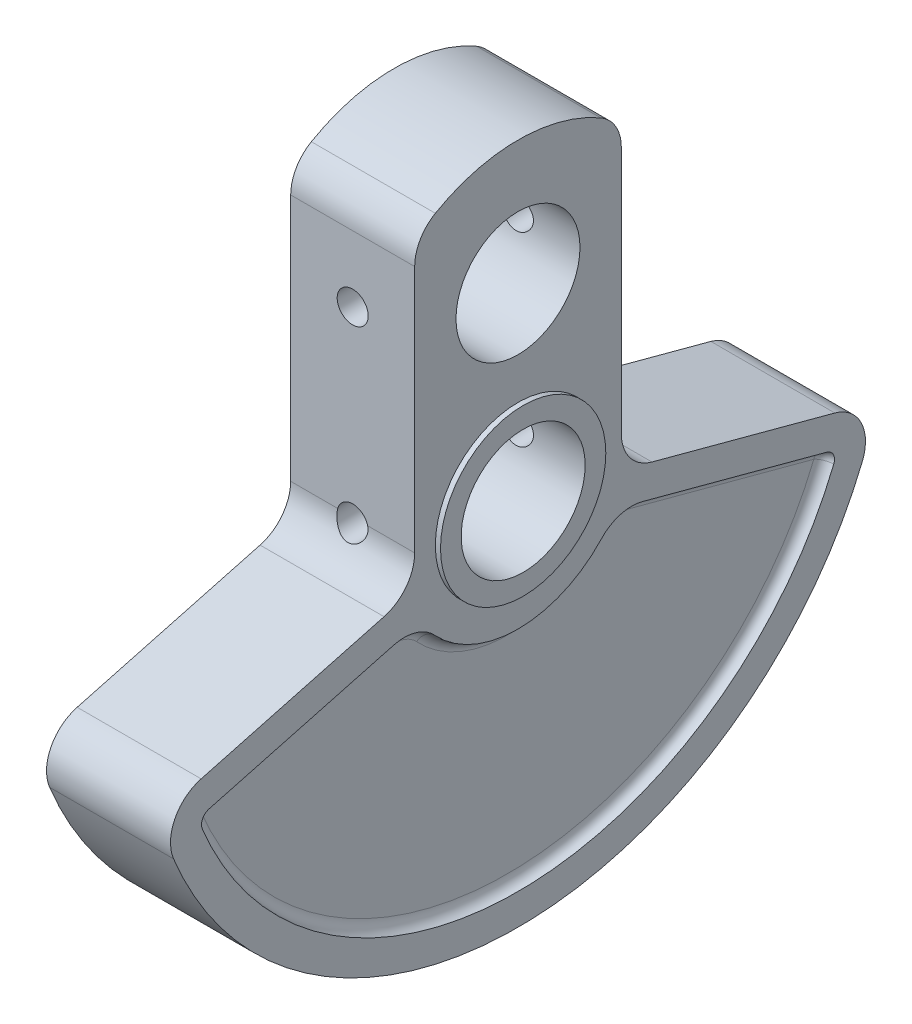
SolidWorks part; units mm, degrees
ref_plane "Front Plane" through (0, 0, 0) normal (0, 0, 1) x (1, 0, 0)
ref_plane "Top Plane" through (0, 0, 0) normal (0, 1, 0) x (1, 0, 0)
ref_plane "Right Plane" through (0, 0, 0) normal (1, 0, 0) x (0, 0, -1)
sketch "Sketch1" plane through (0, 0, 0) normal (1, 0, 0) x (0, 0, -1)
  line L0 (0, 18) -> (0, 0) construction
  line L1 (-12.9647, -3.4739) -> (-30.6672, -8.2172)
  line L2 (12.9647, -3.4739) -> (30.6672, -8.2172)
  line L3 (0, 70.6049) -> (0, -80.6483) construction
  line L4 (-5.7956, -1.5529) -> (0, 0) construction
  line L5 (0, 0) -> (5.7956, -1.5529) construction
  line L6 (-10, 0.3898) -> (-10, 24.3923)
  line L8 (10, 24.3923) -> (10, 0.3898)
  circle A0 centre (0, 0) radius 6
  arc A2 (-33.3359, -13.5911) -> (33.3359, -13.5911) centre (0, 0) ccw
  circle A3 centre (0, 18) radius 6
  arc A4 (30.6672, -8.2172) -> (33.3359, -13.5911) centre (29.6319, -12.081) cw
  arc A5 (-30.6672, -8.2172) -> (-33.3359, -13.5911) centre (-29.6319, -12.081) ccw
  arc A7 (-8, 27.8564) -> (8, 27.8564) centre (0, 14) cw
  arc A8 (8, 27.8564) -> (10, 24.3923) centre (6, 24.3923) cw
  arc A9 (-10, 24.3923) -> (-8, 27.8564) centre (-6, 24.3923) cw
  arc A10 (10, 0.3898) -> (12.9647, -3.4739) centre (14, 0.3898) ccw
  arc A11 (-10, 0.3898) -> (-12.9647, -3.4739) centre (-14, 0.3898) cw
  point P20 (0, 30)
  point P21 (0, 0)
  dimension "D1" = 12
  dimension "D4" = 72
  dimension "D5" = 4
  dimension "D7" = 30
  dimension "D9" = 16
  dimension "D10" = 4
  dimension "D11" = 4
  dimension "D2" = 75
  dimension "D3" = 75
  dimension "D6" = 18
  dimension "D8" = 20
extrude "Boss-Extrude1" add sketch "Sketch1" along normal mid plane 12
sketch "Sketch2" plane through (6, 0, 0) normal (1, 0, 0) x (0, 0, -1)
  line L0 (29.8907, -11.115) -> (12.1883, -6.3717)
  line L3 (-12.1883, -6.3717) -> (-29.8907, -11.115)
  line L4 (30.6672, -8.2172) -> (12.9647, -3.4739)
  line L5 (10, 0.3898) -> (10, 24.3923)
  line L6 (-10, 24.3923) -> (-10, 0.3898)
  line L7 (-12.9647, -3.4739) -> (-30.6672, -8.2172)
  line L8 (30.6672, -8.2172) -> (12.9647, -3.4739)
  line L11 (-12.9647, -3.4739) -> (-30.6672, -8.2172)
  line L12 (10, 0.3898) -> (10, 24.3923) construction
  line L13 (7, 0.3898) -> (7, 24.3923) construction
  line L14 (-7, 24.3923) -> (-7, 0.3898) construction
  line L15 (-10, 24.3923) -> (-10, 0.3898) construction
  line L16 (-12.1883, -6.3717) -> (-12.038, -6.3314)
  line L17 (12.1883, -6.3717) -> (12.038, -6.3314)
  arc A0 (-30.5579, -12.4585) -> (30.5579, -12.4585) centre (0, 0) ccw
  arc A1 (30.5579, -12.4585) -> (29.8907, -11.115) centre (29.6319, -12.081) ccw
  arc A7 (-29.8907, -11.115) -> (-30.5579, -12.4585) centre (-29.6319, -12.081) ccw
  arc A8 (33.3359, -13.5911) -> (30.6672, -8.2172) centre (29.6319, -12.081) ccw
  arc A9 (10, 0.3898) -> (12.9647, -3.4739) centre (14, 0.3898) ccw
  arc A10 (10, 24.3923) -> (8, 27.8564) centre (6, 24.3923) ccw
  arc A11 (8, 27.8564) -> (-8, 27.8564) centre (0, 14) ccw
  arc A12 (-8, 27.8564) -> (-10, 24.3923) centre (-6, 24.3923) ccw
  arc A13 (-12.9647, -3.4739) -> (-10, 0.3898) centre (-14, 0.3898) ccw
  arc A14 (-30.6672, -8.2172) -> (-33.3359, -13.5911) centre (-29.6319, -12.081) ccw
  arc A15 (-33.3359, -13.5911) -> (33.3359, -13.5911) centre (0, 0) ccw
  arc A16 (33.3359, -13.5911) -> (30.6672, -8.2172) centre (29.6319, -12.081) ccw
  arc A21 (-12.9647, -3.4739) -> (-10.8118, -2.0259) centre (-14, 0.3898) ccw
  arc A22 (-30.6672, -8.2172) -> (-33.3359, -13.5911) centre (-29.6319, -12.081) ccw
  arc A23 (-33.3359, -13.5911) -> (33.3359, -13.5911) centre (0, 0) ccw
  arc A24 (-12.9647, -3.4739) -> (-10, 0.3898) centre (-14, 0.3898) ccw construction
  arc A25 (-12.1883, -6.3717) -> (-7, 0.3898) centre (-14, 0.3898) ccw construction
  circle A26 centre (0, 0) radius 11
  arc A27 (-8.0687, -7.4764) -> (8.0687, -7.4764) centre (0, 0) ccw
  arc A28 (7, 0.3898) -> (12.1883, -6.3717) centre (14, 0.3898) ccw construction
  arc A29 (12.038, -6.3314) -> (8.0687, -7.4764) centre (11.0027, -10.1951) ccw
  arc A30 (10, 0.3898) -> (12.9647, -3.4739) centre (14, 0.3898) ccw construction
  arc A31 (10, 24.3923) -> (8, 27.8564) centre (6, 24.3923) ccw construction
  arc A32 (7, 24.3923) -> (6.5, 25.2583) centre (6, 24.3923) ccw construction
  arc A33 (6.5, 25.2583) -> (-6.5, 25.2583) centre (0, 14) ccw construction
  arc A34 (8, 27.8564) -> (-8, 27.8564) centre (0, 14) ccw construction
  arc A35 (-8, 27.8564) -> (-10, 24.3923) centre (-6, 24.3923) ccw construction
  arc A36 (-6.5, 25.2583) -> (-7, 24.3923) centre (-6, 24.3923) ccw construction
  arc A37 (-12.038, -6.3314) -> (-8.0687, -7.4764) centre (-11.0027, -10.1951) cw
  point P40 (9.4459, -5.6369)
  point P46 (0, 0)
  point P47 (9.4459, -5.5563)
  dimension "D4" = 4
  dimension "D1" = 0
  dimension "D2" = 3
  dimension "D3" = 5
extrude "Cut-Extrude1" cut sketch "Sketch2" against normal mid plane 2 contours A37 L16 L3 A7 A0 A1 L0 L17 A29 A27 region at (6, -18.8391, 0)
fillet "Fillet1" radius 1 8 edges at (5, -11, 0) (5, -6.3518, -9.8941) (5, -8.7232, -20.9644) (5, -11.6362, -30.5276) (5, -33, 0) (5, -11.6362, 30.5276) (5, -8.7232, 20.9644) (5, -6.3518, 9.8941)
mirror "Mirror1" about plane through (0, 0, 0) normal (1, 0, 0) of "Cut-Extrude1", "Fillet1"
sketch "Sketch3" plane through (6, 0, 0) normal (1, 0, 0) x (0, 0, -1)
  circle A9 centre (0, 0) radius 8
  circle A10 centre (0, 0) radius 6 construction
  circle A11 centre (0, 0) radius 6
  dimension "D1" = 16
extrude "Boss-Extrude2" add sketch "Sketch3" along normal mid plane 1
sketch "Sketch4" plane through (-6, 0, 0) normal (-1, 0, 0) x (0, 0, 1)
  circle A1 centre (0, 18) radius 8
  circle A2 centre (0, 18) radius 6 construction
  circle A3 centre (0, 18) radius 6
  dimension "D1" = 16
extrude "Boss-Extrude3" add sketch "Sketch4" along normal mid plane 1
sketch "Sketch5" plane through (0, 0, 0) normal (0, 0, 1) x (1, 0, 0)
  line L0 (0, 31.874) -> (0, -43.5402) construction
  line L1 (-6.5, 18) -> (0, 18) construction
  line L2 (-6.5, 26) -> (-6.5, 10) construction
  line L3 (6.5, 0) -> (0, 0) construction
  line L4 (6.5, -8) -> (6.5, 8) construction
  circle A0 centre (0, 18) radius 1.5
  circle A1 centre (0, 0) radius 1.5
  dimension "D1" = 3
  dimension "D2" = 3
extrude "Cut-Extrude2" cut sketch "Sketch5" against normal through all both and the other way through all
